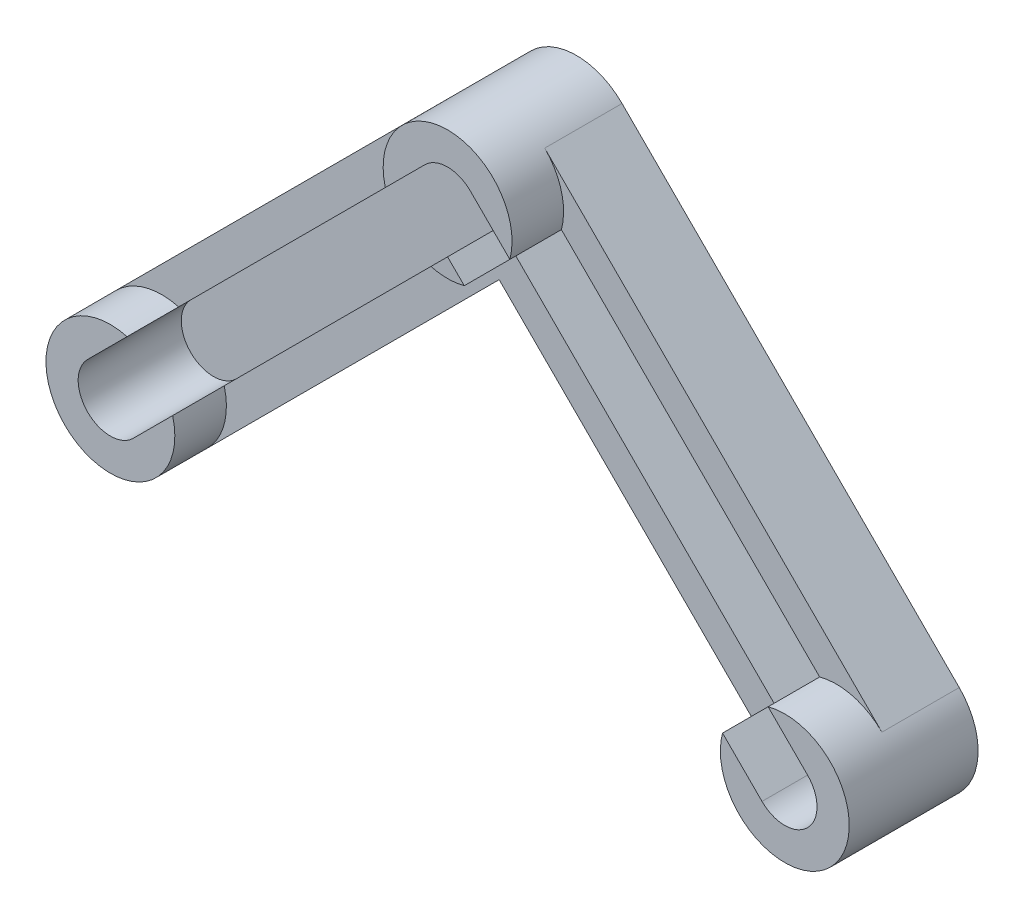
SolidWorks part; units mm, degrees
ref_plane "Спереди" through (0, 0, 0) normal (0, 0, 1) x (1, 0, 0)
ref_plane "Сверху" through (0, 0, 0) normal (0, 1, 0) x (1, 0, 0)
ref_plane "Справа" through (0, 0, 0) normal (1, 0, 0) x (0, 0, -1)
sketch "Эскиз1" plane through (0, 0, 0) normal (0, 0, 1) x (1, 0, 0)
  line L0 (-73.4107, 0) -> (65.3283, 0) construction
  line L1 (-12.0859, 0.4141) -> (-38.2489, -25.7489) construction
  line L2 (-12.0859, 0.4141) -> (14.077, -25.7489) construction
  circle A0 centre (-12.0859, 0.4141) radius 2.5
  circle A1 centre (-12.0859, 0.4141) radius 5
  circle A2 centre (-38.2489, -25.7489) radius 2.5
  circle A3 centre (-38.2489, -25.7489) radius 5
  circle A4 centre (14.077, -25.7489) radius 2.5
  circle A5 centre (14.077, -25.7489) radius 5
  dimension "D2" = 5
  dimension "D3" = 10
  dimension "D5" = 45
  dimension "D1" = 45
  dimension "D4" = 37
  dimension "D6" = 37
extrude "Бобышка-Вытянуть1" add sketch "Эскиз1" along normal blind 10
sketch "Эскиз3" plane through (0, 0, 0) normal (0, 0, -1) x (-1, 0, 0)
  line L0 (12.0859, 0.4141) -> (15.6215, 3.9496)
  line L1 (15.6215, 3.9496) -> (41.7844, -22.2134)
  line L2 (41.7844, -22.2134) -> (34.7133, -29.2844)
  line L3 (34.7133, -29.2844) -> (8.5504, -3.1215)
  line L4 (8.5504, -3.1215) -> (12.0859, 0.4141)
  circle A0 centre (12.0859, 0.4141) radius 5 construction
  circle A1 centre (38.2489, -25.7489) radius 5 construction
extrude "Бобышка-Вытянуть2" add sketch "Эскиз3" against normal blind 6
sketch "Эскиз4" plane through (0, 0, 6) normal (0, 0, 1) x (1, 0, 0)
  line L0 (-13.8537, 2.1818) -> (-10.3181, -1.3537)
  line L1 (-13.8537, 2.1818) -> (-10.3181, -1.3537) construction
  line L2 (-10.3181, -1.3537) -> (-36.4811, -27.5167)
  line L3 (-36.4811, -27.5167) -> (-40.0166, -23.9811) construction
  line L4 (-36.4811, -27.5167) -> (-40.0166, -23.9811)
  line L5 (-40.0166, -23.9811) -> (-13.8537, 2.1818)
  line L6 (-8.5504, -3.1215) -> (-34.7133, -29.2844) construction
  line L8 (-41.7844, -22.2134) -> (-15.6215, 3.9496) construction
  dimension "D1" = 2.5
  dimension "D2" = 2.5
sketch "Эскиз9" plane through (0, 0, 0) normal (0, 0, -1) x (-1, 0, 0)
  line L0 (-14.077, -25.7489) -> (-17.6126, -22.2134)
  line L1 (-17.6126, -22.2134) -> (8.5504, 3.9496)
  line L2 (8.5504, 3.9496) -> (15.6215, -3.1215)
  line L3 (15.6215, -3.1215) -> (-10.5415, -29.2844)
  line L4 (-10.5415, -29.2844) -> (-14.077, -25.7489)
  circle A0 centre (-14.077, -25.7489) radius 5 construction
  arc A1 (15.6215, 3.9496) -> (8.5504, -3.1215) centre (12.0859, 0.4141) ccw construction
extrude "Бобышка-Вытянуть4" add sketch "Эскиз9" against normal blind 6
extrude "Вырез-Вытянуть1" cut sketch "Эскиз4" against normal blind 4
sketch "Эскиз5" plane through (0, 0, 0) normal (0, 0, -1) x (-1, 0, 0)
  line L0 (13.8537, 2.1818) -> (12.0859, 0.4141) construction
  line L1 (36.4811, -27.5167) -> (40.0166, -23.9811) construction
  circle A0 centre (12.9698, 1.2979) radius 3.75
  circle A1 centre (38.2489, -25.7489) radius 2.5
  arc A2 (36.4811, -27.5167) -> (40.0166, -23.9811) centre (38.2489, -25.7489) ccw construction
  arc A3 (13.8537, 2.1818) -> (10.3181, 2.1818) centre (12.0859, 0.4141) ccw construction
extrude "Бобышка-Вытянуть3" add sketch "Эскиз5" against normal blind 2
extrude "Вырез-Вытянуть2" cut sketch "Эскиз4<2>" along normal blind 4
sketch "Эскиз4<2>" plane through (0, 0, 6) normal (0, 0, 1) x (1, 0, 0) same geometry as "Эскиз4"
sketch "Эскиз10" plane through (0, 0, 10) normal (0, 0, 1) x (1, 0, 0)
  line L0 (14.077, -25.7489) -> (12.3093, -27.5167)
  line L1 (12.3093, -27.5167) -> (-13.8537, -1.3537)
  line L2 (-13.8537, -1.3537) -> (-12.0859, 0.4141)
  line L3 (-12.0859, 0.4141) -> (-10.3181, 2.1818)
  line L4 (-10.3181, 2.1818) -> (15.8448, -23.9811)
  line L5 (15.8448, -23.9811) -> (14.077, -25.7489)
  circle A0 centre (14.077, -25.7489) radius 2.5 construction
  arc A1 (-10.3181, -1.3537) -> (-13.8537, 2.1818) centre (-12.0859, 0.4141) ccw construction
extrude "Вырез-Вытянуть3" cut sketch "Эскиз10" against normal blind 8
sketch "Эскиз11" plane through (0, 0, 0) normal (0, 0, -1) x (-1, 0, 0)
  line L0 (-15.8448, -23.9811) -> (-12.3093, -27.5167) construction
  circle A0 centre (-14.077, -25.7489) radius 2.5
  arc A1 (-15.8448, -23.9811) -> (-12.3093, -27.5167) centre (-14.077, -25.7489) ccw construction
extrude "Бобышка-Вытянуть9" add sketch "Эскиз11" against normal blind 2
